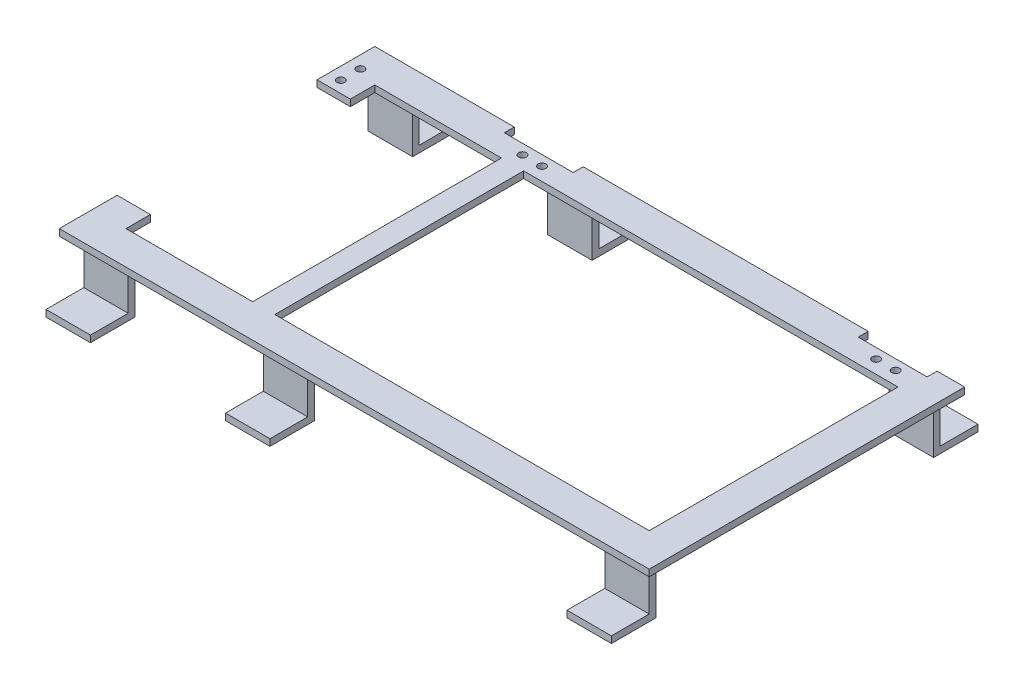
SolidWorks part; units mm, degrees
ref_plane "Alzado" through (0, 0, 0) normal (0, 0, 1) x (1, 0, 0)
ref_plane "Planta" through (0, 0, 0) normal (0, 1, 0) x (1, 0, 0)
ref_plane "Vista lateral" through (0, 0, 0) normal (1, 0, 0) x (0, 0, -1)
sketch "Croquis1" plane through (0, 0, 0) normal (0, 1, 0) x (1, 0, 0)
  line L0 (117.75, 56) -> (-117.75, 56)
  line L1 (132.75, -71) -> (-132.75, -71)
  line L2 (132.75, -71) -> (132.75, 71)
  line L3 (132.75, 71) -> (-132.75, 71)
  line L4 (-132.75, -71) -> (-132.75, 71)
  line L5 (132.75, -71) -> (-132.75, 71) construction
  line L6 (132.75, 71) -> (-132.75, -71) construction
  line L7 (-117.75, -56) -> (-117.75, 56)
  line L8 (117.75, -56) -> (-117.75, -56)
  line L9 (117.75, -56) -> (117.75, 56)
  point P0 (0, 0)
  dimension "D1" = 142
  dimension "D2" = 265.5
  dimension "D3" = 15
extrude "Saliente-Extruir1" add sketch "Croquis1" along normal blind 3
ref_plane "Plano1" through (-127.25, 0, 0) normal (1, 0, 0) x (0, 0, -1)
sketch "Croquis2" plane through (-127.25, 0, 0) normal (-1, 0, 0) x (0, 0, 1)
  line L0 (65.5, 0) -> (65.5, -20)
  line L6 (62.5, 0) -> (65.5, 0)
  line L8 (82.5, -23) -> (82.5, -20)
  line L9 (82.5, -20) -> (65.5, -20)
  line L20 (62.5, 0) -> (62.5, -23)
  line L21 (62.5, -23) -> (82.5, -23)
  line L22 (71, 3) -> (71, 0) construction
  line L23 (-71, 0) -> (71, 0) construction
  dimension "D1" = 23
  dimension "D2" = 3
  dimension "D3" = 5.5
  dimension "D4" = 20
  dimension "D5" = 3
extrude "Saliente-Extruir2" add sketch "Croquis2" against normal blind 20
mirror "Simetría1" about plane through (0, 0, 0) normal (1, 0, 0) of "Saliente-Extruir2"
mirror "Simetría2" about plane through (0, 0, 0) normal (0, 0, 1) of "Simetría1"
sketch "Croquis3" plane through (0, 3, 0) normal (0, 1, 0) x (1, 0, 0)
  line L1 (-120, 32.5) -> (-60, 32.5)
  line L2 (-120, 32.5) -> (-120, -32.5)
  line L3 (-120, -32.5) -> (-60, -32.5)
  line L4 (-60, 32.5) -> (-60, -32.5)
  point P4 (-60, 0)
  dimension "D1" = 65
  dimension "D2" = 60
  dimension "D3" = 60
extrude "Cortar-Extruir1" [suppressed] cut sketch "Croquis3" against normal through all
mirror "Simetría3" [suppressed] about plane through (0, 0, 0) normal (1, 0, 0)
ref_plane "Plano2" through (-36.45, 0, 0) normal (1, 0, 0) x (0, 0, -1)
sketch "Croquis4" plane through (-36.45, 0, 0) normal (1, 0, 0) x (0, 0, -1)
  line L12 (-62.5, 0) -> (-65.5, 0)
  line L13 (-65.5, 0) -> (-65.5, -20)
  line L14 (-65.5, -20) -> (-82.5, -20)
  line L15 (-82.5, -20) -> (-82.5, -23)
  line L16 (-82.5, -23) -> (-62.5, -23)
  line L17 (-82.5, -23) -> (-62.5, -23)
  line L19 (-65.5, 0) -> (-65.5, -20)
  line L20 (-65.5, -20) -> (-82.5, -20)
  line L21 (-82.5, -20) -> (-82.5, -23)
  line L28 (-62.5, 0) -> (-65.5, 0)
  line L38 (-62.5, -23) -> (-62.5, 0)
  line L40 (-62.5, -23) -> (-62.5, 0)
  dimension "D1" = 0
extrude "Saliente-Extruir3" add sketch "Croquis4" along normal mid plane 20
mirror "Simetría4" about plane through (0, 0, 0) normal (0, 0, 1) of "Saliente-Extruir3"
sketch "Croquis5" plane through (0, 3, 0) normal (0, 1, 0) x (1, 0, 0)
  line L1 (-105.499, -45) -> (-143.7054, -45)
  line L2 (-105.499, -45) -> (-105.499, 45)
  line L3 (-105.499, 45) -> (-143.7054, 45)
  line L4 (-143.7054, -45) -> (-143.7054, 45)
  line L5 (-105.499, -45) -> (-143.7054, 45) construction
  line L6 (-105.499, 45) -> (-143.7054, -45) construction
  point P0 (-124.6022, 0)
  dimension "D1" = 90
extrude "Cortar-Extruir2" cut sketch "Croquis5" against normal through all
sketch "Croquis7" plane through (0, 3, 0) normal (0, 1, 0) x (1, 0, 0)
  line L1 (-49.2, 56) -> (-23.2245, 56)
  line L2 (-49.2, 56) -> (-49.2, -56)
  line L3 (-49.2, -56) -> (-23.2245, -56)
  line L4 (-23.2245, 56) -> (-23.2245, -56)
extrude "Cortar-Extruir3" [suppressed] cut sketch "Croquis7" against normal through all
sketch "Croquis6" plane through (0, 3, 0) normal (0, 1, 0) x (1, 0, 0)
  line L0 (-55.75, 56) -> (-55.75, -56) construction
  line L1 (117.75, 56) -> (-117.75, 56) construction
  line L2 (-117.75, -56) -> (117.75, -56) construction
  line L4 (-132.75, -45) -> (-132.75, -71) construction
  line L6 (-60.75, 56) -> (-50.75, 56)
  line L7 (-60.75, 56) -> (-60.75, -56)
  line L8 (-60.75, -56) -> (-50.75, -56)
  line L9 (-50.75, 56) -> (-50.75, -56)
  point P12 (-55.75, 56)
  point P13 (-55.75, -56)
  dimension "D1" = 77
  dimension "D2" = 10
extrude "Saliente-Extruir4" add sketch "Croquis6" against normal up to surface (3 mm away) up to face at (-36.45, 0, -64)
sketch "Croquis8" plane through (0, 3, 0) normal (0, 1, 0) x (1, 0, 0)
  line L0 (132.75, 71) -> (-132.75, 71) construction
  line L1 (120.35, 66.5) -> (89.35, 66.5)
  line L2 (120.35, 66.5) -> (120.35, 71)
  line L3 (120.35, 71) -> (89.35, 71)
  line L4 (89.35, 66.5) -> (89.35, 71)
  line L5 (132.75, -71) -> (132.75, 71) construction
  line L6 (-132.75, 71) -> (-132.75, 45) construction
  line L7 (-38.95, 66.5) -> (-69.95, 66.5)
  line L8 (-38.95, 66.5) -> (-38.95, 71)
  line L9 (-38.95, 71) -> (-69.95, 71)
  line L10 (-69.95, 66.5) -> (-69.95, 71)
  dimension "D1" = 4.5
  dimension "D2" = 12.4
  dimension "D3" = 31
  dimension "D4" = 62.8
extrude "Cortar-Extruir4" cut sketch "Croquis8" against normal blind 10
sketch "Croquis9" plane through (0, 3, 0) normal (0, 1, 0) x (1, 0, 0)
  circle A0 centre (-127.25, 59) radius 1.75
  circle A1 centre (-127.25, 50.2) radius 1.75
extrude "Cortar-Extruir5" cut sketch "Croquis9" against normal through all
sketch "Croquis10" plane through (0, 3, 0) normal (0, 1, 0) x (1, 0, 0)
  circle A0 centre (110.7509, 61.953) radius 1.75
  circle A1 centre (101.9509, 61.953) radius 1.75
  circle A2 centre (-48.4491, 61.953) radius 1.75
  circle A3 centre (-57.2491, 61.953) radius 1.75
extrude "Cortar-Extruir6" cut sketch "Croquis10" against normal blind 20
